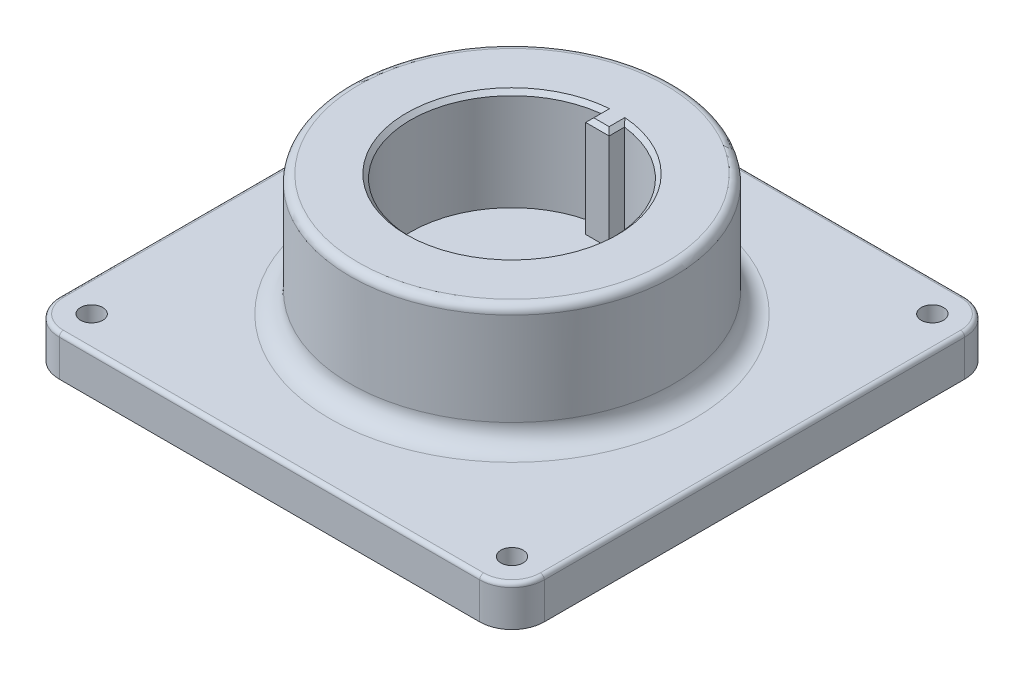
SolidWorks part; units mm, degrees
ref_plane "Front Plane" through (0, 0, 0) normal (0, 0, 1) x (1, 0, 0)
ref_plane "Top Plane" through (0, 0, 0) normal (0, 1, 0) x (1, 0, 0)
ref_plane "Right Plane" through (0, 0, 0) normal (1, 0, 0) x (0, 0, -1)
sketch "Sketch1" plane through (0, 0, 0) normal (0, 1, 0) x (1, 0, 0)
  line L0 (0, 59.5258) -> (0, -57.6138) construction
  line L1 (-78.936, 0) -> (74.7859, 0) construction
  line L3 (-60, -60) -> (60, -60)
  line L4 (-60, -60) -> (-60, 60)
  line L5 (-60, 60) -> (60, 60)
  line L6 (60, -60) -> (60, 60)
  line L7 (-60, -60) -> (60, 60) construction
  line L8 (-60, 60) -> (60, -60) construction
  point P5 (0, 0)
  dimension "D1" = 120
  dimension "D2" = 120
extrude "Boss-Extrude1" add sketch "Sketch1" along normal blind 10
ref_axis "Axis1" through (0, 0, 0) along (0, 1, 0)
sketch "Sketch2" plane through (0, 10, 0) normal (0, 1, 0) x (1, 0, 0)
  line L0 (-60, 60) -> (60, -60) construction
  line L1 (-60, 60) -> (-60, -60) construction
  circle A0 centre (-52, 52) radius 2.75
  dimension "D1" = 5.5
  dimension "D2" = 8
extrude "Cut-Extrude1" cut sketch "Sketch2" against normal through all
pattern_circular "CirPattern1" count 4 over 360 about axis through (0, 0, 0) along (0, 1, 0) of "Cut-Extrude1"
fillet "Fillet1" radius 8 4 edges at (-60, 5, 60) (60, 5, 60) (60, 5, -60) (-60, 5, -60)
fillet "Fillet2" radius 1 8 edges at (-57.6569, 10, -57.6569) (0, 10, -60) (57.6569, 10, -57.6569) (60, 10, 0) (57.6569, 10, 57.6569) (0, 10, 60) (-57.6569, 10, 57.6569) (-60, 10, 0)
sketch "Sketch3" plane through (0, 10, 0) normal (0, 1, 0) x (1, 0, 0)
  circle A0 centre (0, 0) radius 40
  dimension "D1" = 80
extrude "Boss-Extrude2" add sketch "Sketch3" along normal blind 30
sketch "Sketch4" plane through (0, 40, 0) normal (0, 1, 0) x (1, 0, 0)
  circle A0 centre (0, 0) radius 25.1
  dimension "D1" = 50.2
extrude "Cut-Extrude2" cut sketch "Sketch4" against normal blind 25
sketch "Sketch5" plane through (0, 40, 0) normal (0, 1, 0) x (1, 0, 0)
  line L0 (0, 0) -> (0, 32.3516) construction
  line L1 (2.9, 21.1319) -> (-2.9, 21.1319)
  line L2 (-2.9, 21.1319) -> (-2.9, 24.9319)
  line L3 (2.9, 21.1319) -> (2.9, 24.9319)
  circle A0 centre (0, 0) radius 25.1 construction
  circle A1 centre (0, 0) radius 25.1 construction
  arc A2 (2.9, 24.9319) -> (-2.9, 24.9319) centre (0, 0) ccw
  point P9 (0, 21.1319)
  dimension "D1" = 5.8
  dimension "D2" = 3.8
extrude "Boss-Extrude3" add sketch "Sketch5" against normal up to next
chamfer "Chamfer1" distance 1 angle 45 4 edges at (-2.9, 40, -23.0319) (0, 40, -21.1319) (2.9, 40, -23.0319) (0, 40, 25.1)
fillet "Fillet3" radius 2 1 edges at (0, 40, 40)
fillet "Fillet4" radius 5 1 edges at (0, 10, -40)
